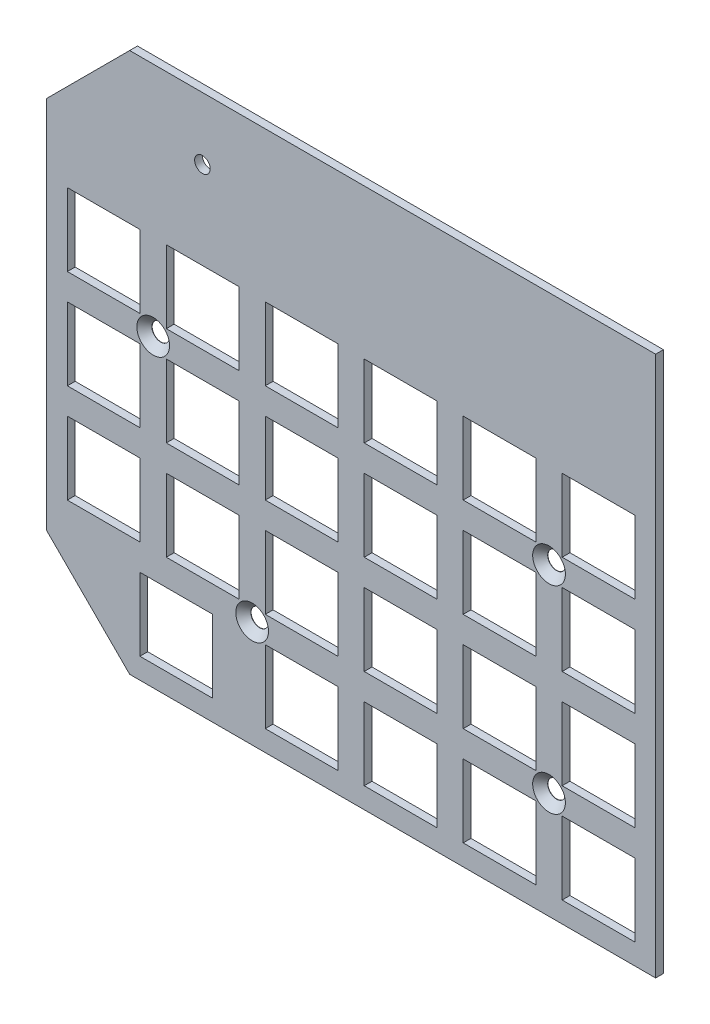
SolidWorks part; units mm, degrees
material "Alliage 1060"
ref_plane "Plan de face" through (0, 0, 0) normal (0, 0, 1) x (1, 0, 0)
ref_plane "Plan de dessus" through (0, 0, 0) normal (0, 1, 0) x (1, 0, 0)
ref_plane "Plan de droite" through (0, 0, 0) normal (1, 0, 0) x (0, 0, -1)
other "Centre de masse"
sketch "Esquisse1" plane through (0, 0, 0) normal (0, 0, 1) x (1, 0, 0)
  line L0 (0, -85) -> (16, -101)
  line L4 (117.25, 3) -> (117.25, -101)
  line L5 (16, 3) -> (0, -13)
  line L7 (117.25, 3) -> (16, 3)
  line L8 (0, -13) -> (0, -85)
  line L9 (16, -101) -> (117.25, -101)
  dimension "D1" = 104
  dimension "D2" = 117.25
  dimension "D3" = 16
  dimension "D4" = 16
  dimension "D5" = 16
  dimension "D6" = 16
extrude "Boss.-Extru.1" add sketch "Esquisse1" along normal blind 1.5
sketch "Esquisse2" plane through (0, 0, 1.5) normal (0, 0, 1) x (1, 0, 0)
  line L0 (0, -13) -> (0, -85) construction
  line L1 (4, -25.85) -> (18, -25.85)
  line L2 (4, -25.85) -> (4, -39.85)
  line L3 (4, -39.85) -> (18, -39.85)
  line L4 (18, -25.85) -> (18, -39.85)
  line L5 (11, -39.85) -> (11, -25.85) construction
  line L6 (4, -32.85) -> (18, -32.85) construction
  line L7 (117.25, 3) -> (16, 3) construction
  line L8 (117.25, -101) -> (117.25, 3) construction
  line L12 (23.05, -25.85) -> (23.05, -39.85)
  line L13 (23.05, -25.85) -> (37.05, -25.85)
  line L14 (37.05, -25.85) -> (37.05, -39.85)
  line L15 (23.05, -39.85) -> (37.05, -39.85)
  line L16 (42.1, -25.85) -> (42.1, -39.85)
  line L17 (42.1, -25.85) -> (56.1, -25.85)
  line L18 (56.1, -25.85) -> (56.1, -39.85)
  line L19 (42.1, -39.85) -> (56.1, -39.85)
  line L20 (61.15, -25.85) -> (61.15, -39.85)
  line L21 (61.15, -25.85) -> (75.15, -25.85)
  line L22 (75.15, -25.85) -> (75.15, -39.85)
  line L23 (61.15, -39.85) -> (75.15, -39.85)
  line L24 (80.2, -25.85) -> (80.2, -39.85)
  line L25 (80.2, -25.85) -> (94.2, -25.85)
  line L26 (94.2, -25.85) -> (94.2, -39.85)
  line L27 (80.2, -39.85) -> (94.2, -39.85)
  line L28 (99.25, -25.85) -> (99.25, -39.85)
  line L29 (99.25, -25.85) -> (113.25, -25.85)
  line L30 (113.25, -25.85) -> (113.25, -39.85)
  line L31 (99.25, -39.85) -> (113.25, -39.85)
  line L32 (23.05, -44.9) -> (23.05, -58.9)
  line L33 (23.05, -44.9) -> (37.05, -44.9)
  line L34 (37.05, -44.9) -> (37.05, -58.9)
  line L35 (23.05, -58.9) -> (37.05, -58.9)
  line L36 (42.1, -44.9) -> (42.1, -58.9)
  line L37 (42.1, -44.9) -> (56.1, -44.9)
  line L38 (56.1, -44.9) -> (56.1, -58.9)
  line L39 (42.1, -58.9) -> (56.1, -58.9)
  line L40 (61.15, -44.9) -> (61.15, -58.9)
  line L41 (61.15, -44.9) -> (75.15, -44.9)
  line L42 (75.15, -44.9) -> (75.15, -58.9)
  line L43 (61.15, -58.9) -> (75.15, -58.9)
  line L44 (80.2, -44.9) -> (80.2, -58.9)
  line L45 (80.2, -44.9) -> (94.2, -44.9)
  line L46 (94.2, -44.9) -> (94.2, -58.9)
  line L47 (80.2, -58.9) -> (94.2, -58.9)
  line L48 (99.25, -44.9) -> (99.25, -58.9)
  line L49 (99.25, -44.9) -> (113.25, -44.9)
  line L50 (113.25, -44.9) -> (113.25, -58.9)
  line L51 (99.25, -58.9) -> (113.25, -58.9)
  line L52 (23.05, -63.95) -> (23.05, -77.95)
  line L53 (23.05, -63.95) -> (37.05, -63.95)
  line L54 (37.05, -63.95) -> (37.05, -77.95)
  line L55 (23.05, -77.95) -> (37.05, -77.95)
  line L56 (42.1, -63.95) -> (42.1, -77.95)
  line L57 (42.1, -63.95) -> (56.1, -63.95)
  line L58 (56.1, -63.95) -> (56.1, -77.95)
  line L59 (42.1, -77.95) -> (56.1, -77.95)
  line L60 (61.15, -63.95) -> (61.15, -77.95)
  line L61 (61.15, -63.95) -> (75.15, -63.95)
  line L62 (75.15, -63.95) -> (75.15, -77.95)
  line L63 (61.15, -77.95) -> (75.15, -77.95)
  line L64 (80.2, -63.95) -> (80.2, -77.95)
  line L65 (80.2, -63.95) -> (94.2, -63.95)
  line L66 (94.2, -63.95) -> (94.2, -77.95)
  line L67 (80.2, -77.95) -> (94.2, -77.95)
  line L68 (99.25, -63.95) -> (99.25, -77.95)
  line L69 (99.25, -63.95) -> (113.25, -63.95)
  line L70 (113.25, -63.95) -> (113.25, -77.95)
  line L71 (99.25, -77.95) -> (113.25, -77.95)
  line L72 (4, -44.9) -> (4, -58.9)
  line L73 (4, -44.9) -> (18, -44.9)
  line L74 (18, -44.9) -> (18, -58.9)
  line L75 (4, -58.9) -> (18, -58.9)
  line L76 (4, -63.95) -> (4, -77.95)
  line L77 (4, -63.95) -> (18, -63.95)
  line L78 (18, -63.95) -> (18, -77.95)
  line L79 (4, -77.95) -> (18, -77.95)
  line L112 (42.1, -83) -> (42.1, -97)
  line L113 (42.1, -83) -> (56.1, -83)
  line L114 (56.1, -83) -> (56.1, -97)
  line L115 (42.1, -97) -> (56.1, -97)
  line L116 (61.15, -83) -> (61.15, -97)
  line L117 (61.15, -83) -> (75.15, -83)
  line L118 (75.15, -83) -> (75.15, -97)
  line L119 (61.15, -97) -> (75.15, -97)
  line L120 (80.2, -83) -> (80.2, -97)
  line L121 (80.2, -83) -> (94.2, -83)
  line L122 (94.2, -83) -> (94.2, -97)
  line L123 (80.2, -97) -> (94.2, -97)
  line L124 (99.25, -83) -> (99.25, -97)
  line L125 (99.25, -83) -> (113.25, -83)
  line L126 (113.25, -83) -> (113.25, -97)
  line L127 (99.25, -97) -> (113.25, -97)
  line L128 (4, -83) -> (4, -97) [skipped]
  line L129 (4, -83) -> (18, -83) [skipped]
  line L130 (18, -83) -> (18, -97) [skipped]
  line L131 (4, -97) -> (18, -97) [skipped]
  line L132 (23.05, -83) -> (23.05, -97) [skipped]
  line L133 (23.05, -83) -> (37.05, -83) [skipped]
  line L134 (37.05, -83) -> (37.05, -97) [skipped]
  line L135 (23.05, -97) -> (37.05, -97) [skipped]
  line L137 (17.97, -83) -> (31.97, -83)
  line L138 (17.97, -83) -> (17.97, -97)
  line L139 (17.97, -97) -> (31.97, -97)
  line L140 (31.97, -83) -> (31.97, -97)
  line L141 (24.97, -97) -> (24.97, -83) construction
  line L142 (17.97, -90) -> (31.97, -90) construction
  line L143 (16, -101) -> (117.25, -101) construction
  circle A8 centre (30, -9) radius 1.5
  point P0 (11, -32.85)
  point P19 (24.97, -90)
  dimension "D5" = 4
  dimension "D13" = 5.05
  dimension "D7" = 12
  dimension "D6" = 30
  dimension "D1" = 14
  dimension "D2" = 14
  dimension "D3" = 4
  dimension "D4" = 6
  dimension "D9" = 14
  dimension "D10" = 14
  dimension "D11" = 10.13
  dimension "D12" = 5.05
  dimension "D8" = 4
extrude "Enlèv. mat.-Extru.1" cut sketch "Esquisse2" against normal blind 1.5
sketch "Esquisse9" plane through (0, 0, 1.5) normal (0, 0, 1) x (1, 0, 0)
  line L0 (18, -44.9) -> (23.05, -39.85) construction
  line L1 (94.2, -39.85) -> (99.25, -44.9) construction
  line L2 (94.2, -83) -> (99.25, -77.95) construction
  line L3 (37.05, -77.95) -> (42.1, -83) construction
  point P16 (20.525, -42.375)
  point P17 (39.575, -80.475)
  point P18 (96.725, -42.375)
  point P19 (96.725, -80.475)
hole_wizard "Fraisage pour vis à tête fraisée M31" positions "Esquisse17" profile "Esquisse18" countersink size "M3" standard "Ansi Metric" end condition through all
sketch "Esquisse17" plane through (0, 0, 1.5) normal (0, 0, 1) x (1, 0, 0)
  point P0 (20.525, -42.375)
  point P4 (96.725, -42.375)
  point P7 (96.725, -80.475)
  point P10 (39.575, -80.475)
sketch "Esquisse18" plane through (20.525, -42.375, 1.5) normal (1, 0, 0) x (0, -1, 0)
  line L0 (0, 0) -> (0, 1.5)
  line L1 (0, 1.5) -> (1.7, 1.5)
  line L2 (1.7, 1.5) -> (1.7, 1.45)
  line L3 (1.7, 1.45) -> (3.15, 0)
  line L5 (3.15, 0) -> (0, 0)
  line L6 (-1.7, 1.45) -> (-3.15, 0) construction
  line L11 (0, -6.35) -> (0, 107.95) construction
  dimension "Diamètre du perçage jusqu'au prochain" = 3.4
  dimension "Profondeur du perçage jusqu'au prochain" = 1.5
  dimension "Diamètre du fraisage entrant" = 6.3
  dimension "Angle du fraisage entrant" = 90
